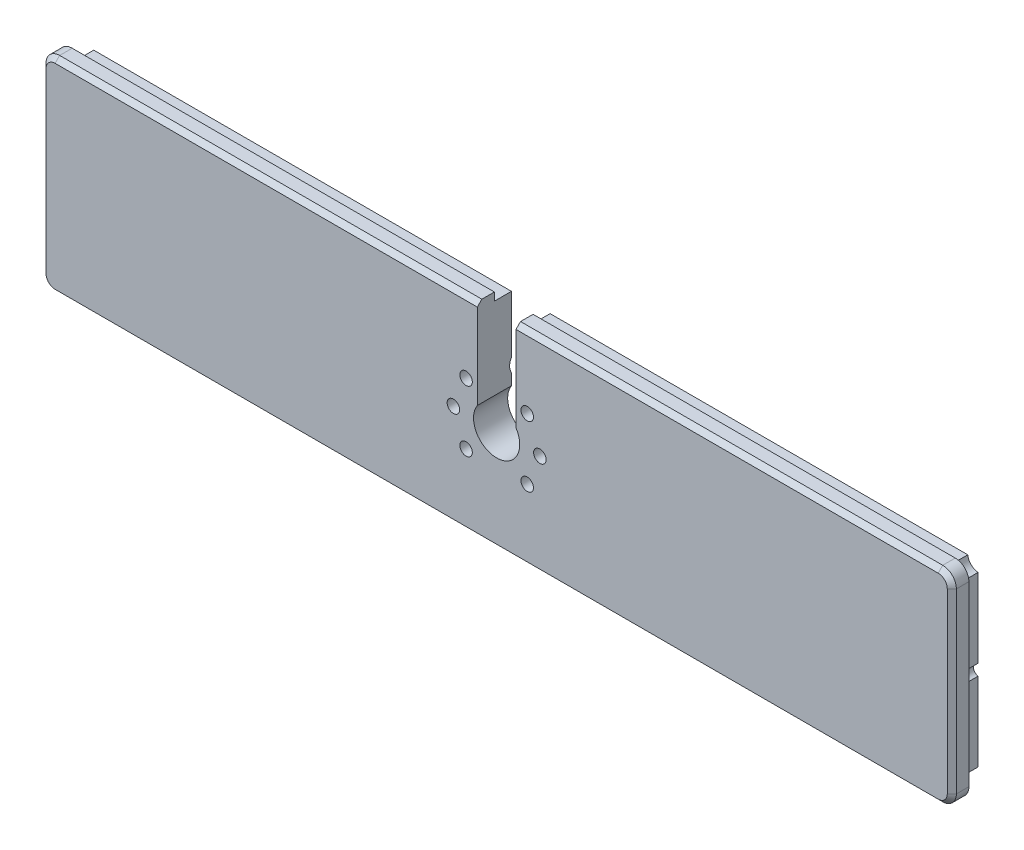
SolidWorks part; units mm, degrees
material "PET"
ref_plane "Front Plane" through (0, 0, 0) normal (0, 0, 1) x (1, 0, 0)
ref_plane "Top Plane" through (0, 0, 0) normal (0, 1, 0) x (1, 0, 0)
ref_plane "Right Plane" through (0, 0, 0) normal (1, 0, 0) x (0, 0, -1)
sketch "Sketch1" plane through (0, 0, 0) normal (0, 0, 1) x (1, 0, 0)
  line L1 (200, -45) -> (-200, -45)
  line L2 (200, -45) -> (200, 45)
  line L3 (200, 45) -> (-200, 45)
  line L4 (-200, -45) -> (-200, 45)
  line L5 (200, -45) -> (-200, 45) construction
  line L6 (200, 45) -> (-200, -45) construction
  point P0 (0, 0)
  dimension "D1" = 90
  dimension "D2" = 400
extrude "Boss-Extrude1" add sketch "Sketch1" against normal blind 7.5
sketch "Sketch2" plane through (0, 0, -7.5) normal (0, 0, -1) x (-1, 0, 0)
  line L8 (196.5, -41.5) -> (196.5, 41.5)
  line L9 (196.5, 41.5) -> (-196.5, 41.5)
  line L10 (-196.5, 41.5) -> (-196.5, -41.5)
  line L11 (-196.5, -41.5) -> (196.5, -41.5)
  line L12 (196.5, -41.5) -> (196.5, 41.5)
  line L13 (196.5, 41.5) -> (-196.5, 41.5)
  line L14 (-196.5, 41.5) -> (-196.5, -41.5)
  line L15 (-196.5, -41.5) -> (196.5, -41.5)
extrude "Boss-Extrude2" add sketch "Sketch2" along normal blind 7.5
sketch "Sketch3" plane through (0, 0, 0) normal (0, 0, 1) x (1, 0, 0)
  line L0 (0, 0) -> (0, 51.1675) construction
  line L1 (200, 45) -> (-200, 45) construction
  line L2 (8.5, 5.5473) -> (-8.5, 5.5473) construction
  line L3 (8.5, 5.5473) -> (8.5, 45)
  line L4 (8.5, 45) -> (-8.5, 45)
  line L5 (-8.5, 5.5473) -> (-8.5, 45)
  line L6 (8.5, 5.5473) -> (-8.5, 45) construction
  line L7 (8.5, 45) -> (-8.5, 5.5473) construction
  line L8 (0, 0) -> (-19, 0) construction
  arc A0 (-8.5, 5.5473) -> (8.5, 5.5473) centre (0, 0) ccw
  circle A1 centre (-19, 0) radius 2.75
  circle A2 centre (-13.435, 13.435) radius 2.75
  circle A3 centre (0, 19) radius 2.75 construction
  circle A4 centre (13.435, 13.435) radius 2.75
  circle A5 centre (19, 0) radius 2.75
  circle A6 centre (13.435, -13.435) radius 2.75
  circle A7 centre (0, -19) radius 2.75 construction
  circle A8 centre (-13.435, -13.435) radius 2.75
  point P3 (0, 25.2736)
  point P28 (0, 0)
  dimension "D4" = 5.5
  dimension "D2" = 17
  dimension "D3" = 19
  dimension "D5" = 8
extrude "Cut-Extrude1" cut sketch "Sketch3" against normal through all
fillet "Fillet1" radius 6 4 edges at (200, -45, -3.75) (-200, -45, -3.75) (-200, 45, -3.75) (200, 45, -3.75)
sketch "Sketch4" plane through (0, 0, -15) normal (0, 0, -1) x (-1, 0, 0)
  line L0 (-197, 42) -> (-197, -42) construction
  line L1 (-200, -39) -> (-200, 39) construction
  line L2 (-194, 45) -> (-8.5, 45) construction
  line L4 (194, -45) -> (-194, -45) construction
  line L5 (-197, -42) -> (0, -42) construction
  line L6 (0, 0) -> (0, -42) construction
  circle A0 centre (-197, 42) radius 5
  circle A1 centre (-197, -42) radius 5
  circle A2 centre (-197, 0) radius 2.5
  circle A3 centre (0, -42) radius 2.5
  circle A4 centre (197, -42) radius 5
  circle A5 centre (197, 0) radius 2.5
  circle A6 centre (197, 42) radius 5
  dimension "D4" = 5
  dimension "D5" = 10
  dimension "D1" = 3
  dimension "D2" = 3
  dimension "D3" = 3
extrude "Cut-Extrude2" cut sketch "Sketch4" against normal up to surface (7.5 mm away) up to face at (0, 10.8125, -7.5)
chamfer "Chamfer1" distance 2 angle 45 9 edges at (-101.25, 45, 0) (-198.2426, 43.2426, 0) (-200, 0, 0) (-198.2426, -43.2426, 0) (0, -45, 0) (198.2426, -43.2426, 0) (200, 0, 0) (198.2426, 43.2426, 0) (101.25, 45, 0)
chamfer "Chamfer2" distance 3 angle 45 6 edges at (16.185, -13.435, -15) (-16.25, 0, -15) (-10.685, -13.435, -15) (21.75, 0, -15) (16.185, 13.435, -15) (-10.685, 13.435, -15)
equation "\"hole_radius\"= 10.15mm"
equation "\"D1@Sketch3\"=\"hole_radius\"*2"
equation "\"M5_tap\"=4.2mm"
equation "\"M5_clearence\"=5.5mm"
equation "\"M6_tap\"=5mm"
equation "\"M6_clearence\"=6.6mm"
equation "\"work_area_width\"=1100mm"
equation "\"work_area_depth\"=900mm"
equation "\"steel_base_width\"=80mm"
equation "\"steel_base_height\"=50mm"
equation "\"steel_base_wall_thickness\"=3mm"
equation "\"steel_base_radius\"=6mm"
equation "\"steel_sides_width\"=180mm"
equation "\"steel_sides_height\"=50mm"
equation "\"steel_sides_wall_thickness\"=5mm"
equation "\"steel_sides_radius\"=6mm"
equation "\"steel_gantry_width\"=120mm"
equation "\"steel_gantry_height\"=80mm"
equation "\"steel_gantry_wall_thickness\"=6mm"
equation "\"steel_gantry_radius\"=6mm"
equation "\"steel_rollers_width\"=80mm"
equation "\"steel_rollers_height\"=50mm"
equation "\"steel_rollers_wall_thickness\"=6mm"
equation "\"steel_rollers_radius\"=6mm"
equation "\"steel_zbox_width\"=400mm"
equation "\"steel_zbox_height\"=90mm"
equation "\"steel_zbox_wall_thickness\"=3mm"
equation "\"steel_zbox_radius\"=6mm"
equation "\"D2@Sketch1\"=\"steel_zbox_width\""
equation "\"D1@Sketch1\"=\"steel_zbox_height\""
equation "\"D1@Sketch2\"=\"steel_zbox_wall_thickness\"+ 0.5mm"
equation "\"D1@Fillet1\"=\"steel_zbox_radius\""
